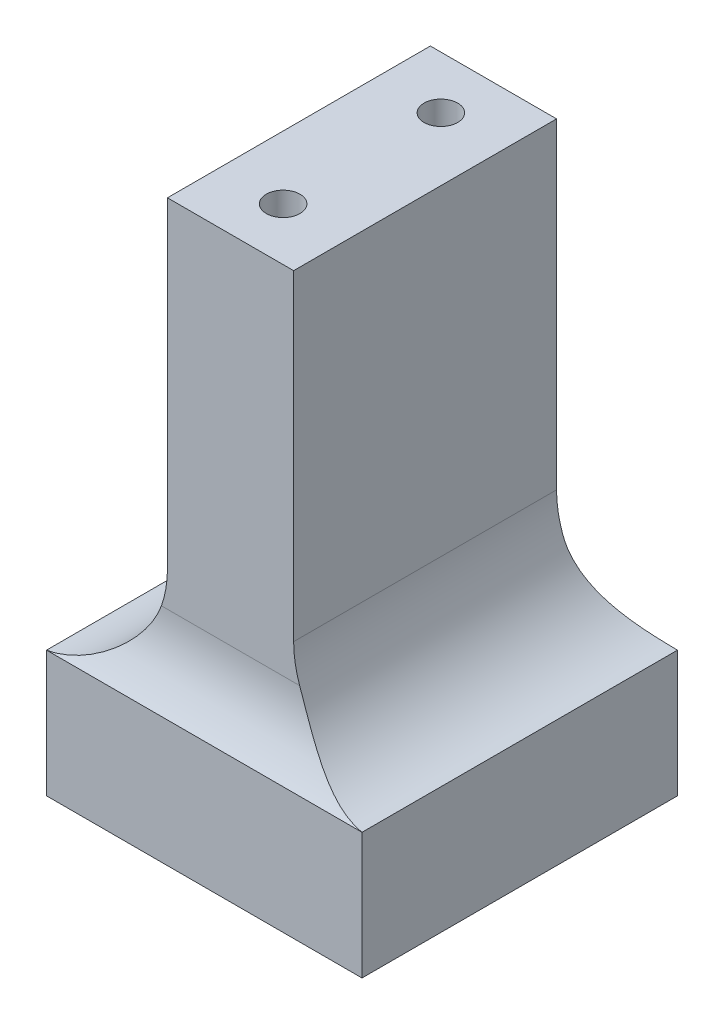
SolidWorks part; units mm, degrees
ref_plane "Front Plane" through (0, 0, 0) normal (0, 0, 1) x (1, 0, 0)
ref_plane "Top Plane" through (0, 0, 0) normal (0, 1, 0) x (1, 0, 0)
ref_plane "Right Plane" through (0, 0, 0) normal (1, 0, 0) x (0, 0, -1)
sketch "Sketch1" plane through (0, 0, 0) normal (0, 1, 0) x (1, 0, 0)
  line L1 (15, -15) -> (-15, -15)
  line L2 (15, -15) -> (15, 15)
  line L3 (15, 15) -> (-15, 15)
  line L4 (-15, -15) -> (-15, 15)
  line L5 (15, -15) -> (-15, 15) construction
  line L6 (15, 15) -> (-15, -15) construction
  point P0 (0, 0)
  dimension "D1" = 30
extrude "Boss-Extrude1" add sketch "Sketch1" along normal blind 12
sketch "Sketch2" plane through (0, 12, 0) normal (0, 1, 0) x (1, 0, 0)
  line L0 (-15, 0) -> (15, 0) construction
  line L1 (-15, 15) -> (-15, -15) construction
  line L2 (15, -15) -> (15, 15) construction
  line L3 (0, 12.5) -> (0, -12.5) construction
  line L4 (6, 12.5) -> (-6, 12.5)
  line L5 (6, 12.5) -> (6, -12.5)
  line L6 (6, -12.5) -> (-6, -12.5)
  line L7 (-6, 12.5) -> (-6, -12.5)
  dimension "D1" = 12
  dimension "D2" = 25
extrude "Boss-Extrude2" add sketch "Sketch2" along normal blind 40.5
sketch "Sketch3" plane through (0, 52.5, 0) normal (0, 1, 0) x (1, 0, 0)
  line L0 (0, 12.5) -> (0, -12.5) construction
  line L1 (6, 12.5) -> (-6, 12.5) construction
  line L2 (-6, -12.5) -> (6, -12.5) construction
  circle A0 centre (0, -7.5) radius 1.6
  circle A1 centre (0, 7.5) radius 1.6
  point P12 (-8.8794, 3.254)
  dimension "D1" = 3.2
  dimension "D2" = 5
  dimension "D3" = 15
extrude "Cut-Extrude1" cut sketch "Sketch3" against normal blind 10
fillet "Fillet1" radius 10 4 edges at (0, 12, -12.5) (-6, 12, 0) (0, 12, 12.5) (6, 12, 0)
